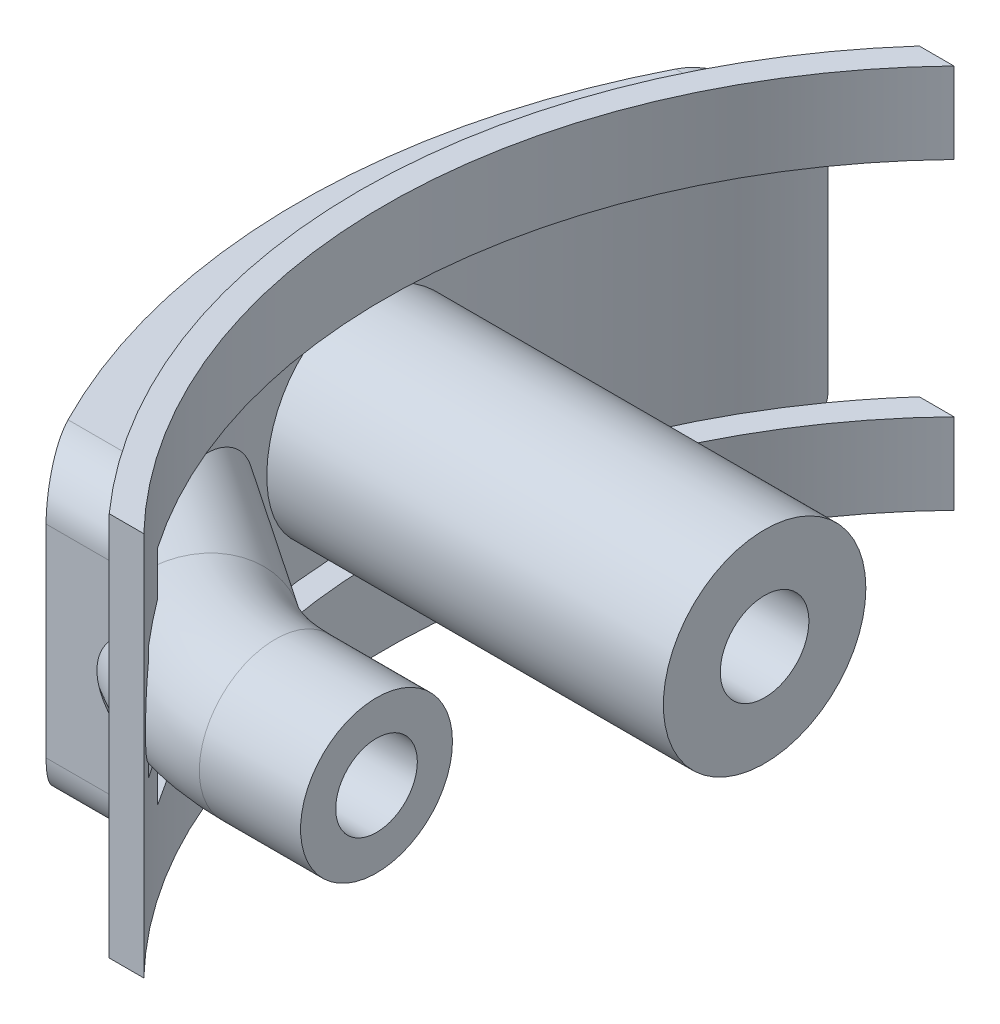
SolidWorks part; units mm, degrees
ref_plane "Front Plane" through (0, 0, 0) normal (0, 0, 1) x (1, 0, 0)
ref_plane "Top Plane" through (0, 0, 0) normal (0, 1, 0) x (1, 0, 0)
ref_plane "Right Plane" through (0, 0, 0) normal (1, 0, 0) x (0, 0, -1)
sketch "Sketch1" plane through (0, 0, 0) normal (0, 1, 0) x (1, 0, 0)
  line L0 (-71.0633, 44.45) -> (-61.8921, 44.45)
  line L1 (-71.0633, -44.45) -> (-61.8921, -44.45)
  line L2 (0, 0) -> (-76.2, 0) construction
  arc A0 (-71.0633, 44.45) -> (-71.0633, -44.45) centre (0, 0) ccw
  arc A1 (-61.8921, 44.45) -> (-61.8921, -44.45) centre (0, 0) ccw
  dimension "D1" = 167.64
  dimension "D2" = 152.4
  dimension "D3" = 88.9
extrude "Boss-Extrude1" add sketch "Sketch1" along normal blind 19.05 and the other way blind 19.05
sketch "Sketch14" plane through (0, 0, 0) normal (1, 0, 0) x (0, 0, -1)
  line L0 (-44.45, -19.05) -> (-44.45, 19.05) construction
  line L1 (-50.8, 24.13) -> (50.8, 24.13)
  line L2 (-50.8, 24.13) -> (-50.8, 13.97)
  line L3 (-50.8, 13.97) -> (50.8, 13.97)
  line L4 (50.8, 24.13) -> (50.8, 13.97)
  line L5 (44.45, -19.05) -> (44.45, 19.05) construction
  line L6 (-50.8, 19.05) -> (50.8, 19.05) construction
  line L7 (44.45, 19.05) -> (-44.45, 19.05) construction
  line L8 (-49.7824, 0) -> (49.7824, 0) construction
  line L9 (-50.8, -19.05) -> (50.8, -19.05) construction
  line L10 (50.8, -24.13) -> (50.8, -13.97)
  line L11 (-50.8, -13.97) -> (50.8, -13.97)
  line L12 (-50.8, -24.13) -> (-50.8, -13.97)
  line L13 (-50.8, -24.13) -> (50.8, -24.13)
  dimension "D1" = 10.16
  dimension "D2" = 6.35
  dimension "D3" = 6.35
extrude "Boss-Extrude11" add sketch "Sketch14" against normal up to surface (5.9961 mm away) from offset 50.8 up to face at (-69.0461, 0, 0) offset against normal yes
sketch "Sketch15" plane through (0, 24.13, 0) normal (0, 1, 0) x (1, 0, 0)
  line L0 (-51.6365, -51.6365) -> (-53.8815, -53.8815)
  line L1 (-53.8815, 53.8815) -> (-51.6365, 51.6365)
  line L2 (0, 0) -> (-123.1347, 0) construction
  arc A0 (-51.6365, 51.6365) -> (-51.6365, -51.6365) centre (0, 0) ccw
  arc A1 (-56.7961, 50.8) -> (-56.7961, -50.8) centre (0, 0) ccw construction
  arc A2 (-53.8815, -53.8815) -> (-53.8815, 53.8815) centre (0, 0) ccw
  dimension "D1" = 146.05
  dimension "D2" = 90
extrude "Cut-Extrude1" cut sketch "Sketch15" against normal up to next
sketch "Sketch17" plane through (0, 13.97, 0) normal (0, -1, 0) x (1, 0, 0)
  line L0 (-64.0532, 41.275) -> (-60.2414, 41.275)
  line L1 (-56.7961, 50.8) -> (-52.4596, 50.8) construction
  line L3 (-52.4596, 50.8) -> (-56.7961, 50.8)
  arc A0 (-61.8921, 44.45) -> (-61.8921, -44.45) centre (0, 0) ccw construction
  arc A1 (-52.4596, 50.8) -> (-52.4596, -50.8) centre (0, 0) ccw construction
  arc A2 (-52.4596, 50.8) -> (-60.2414, 41.275) centre (0, 0) ccw
  arc A4 (-64.0532, 41.275) -> (-56.7961, 50.8) centre (0, 0) cw
  dimension "D1" = 9.525
extrude "Boss-Extrude12" add sketch "Sketch17" along normal up to surface (27.94 mm away) up to face at (-58.909, -13.97, 0)
mirror "Mirror4" about plane through (0, 0, 0) normal (0, 1, 0) of "Cut-Extrude1"
sketch "Sketch2" plane through (0, 0, 0) normal (1, 0, 0) x (0, 0, -1)
  circle A0 centre (0, 0) radius 12.7
  dimension "D1" = 25.4
extrude "Boss-Extrude2" add sketch "Sketch2" against normal up to surface (49.7342 mm away) from offset 25.4 up to face at (-69.5742, 0, -1.7539) offset against normal yes
ref_axis "Axis1" through (0, -13.97, 0) along (0, 1, 0)
sketch "Sketch6" plane through (0, 0, 0) normal (0, 1, 0) x (1, 0, 0)
  line L0 (0, 0) -> (-83.82, 0) construction
  line L1 (-25.4, 5.5562) -> (-51.2095, 5.5562)
  line L2 (-25.4, -12.7) -> (-25.4, 12.7) construction
  line L3 (-57.5595, 3.8548) -> (-60.2451, 2.3042)
  line L4 (-61.2611, 0) -> (-61.2611, 2.032) construction
  line L5 (-62.05, 2.1359) -> (-83.4497, 7.8699)
  line L6 (-25.4, 5.5562) -> (-25.4, 0)
  line L7 (-25.4, 0) -> (-83.82, 0)
  line L8 (-83.82, 0) -> (-83.82, 7.8699)
  line L9 (-83.82, 7.8699) -> (-83.4497, 7.8699)
  arc A0 (-71.0633, 44.45) -> (-71.0633, -44.45) centre (0, 0) ccw construction
  arc A1 (-61.2611, 2.032) -> (-60.2451, 2.3042) centre (-61.2611, 4.064) ccw
  arc A2 (-62.05, 2.1359) -> (-61.2611, 2.032) centre (-61.2611, 5.08) ccw
  arc A3 (-51.2095, 5.5562) -> (-57.5595, 3.8548) centre (-51.2095, -7.1438) ccw
  dimension "D2" = 2.032
  dimension "D3" = 3.048
  dimension "D7" = 12.7
  dimension "D1" = 2.032
  dimension "D4" = 15
  dimension "D5" = 7.8699
  dimension "D6" = 5.5562
  dimension "D8" = 30
revolve "Cut-Revolve1" cut sketch "Sketch6" angle 360 about L0
ref_plane "Plane3" through (0, 0, 0) normal (-0.829, 0, -0.5592) x (-0.5592, 0, 0.829)
sketch "Sketch7" plane through (0, 0, 0) normal (-0.829, 0, -0.5592) x (-0.5592, 0, 0.829)
  line L0 (0, -13.97) -> (0, 13.97) construction
  circle A0 centre (63.5, 0) radius 9.525
  dimension "D1" = 19.05
  dimension "D2" = 63.5
extrude "Boss-Extrude4" add sketch "Sketch7" along normal up to surface (0.1767 mm away) from offset 21.59 up to face at (-75.1836, -2.7246, 12.4043)
sketch "Sketch10" plane through (0, 0, 0) normal (0, 1, 0) x (1, 0, 0)
  line L0 (-59.7733, -36.2772) -> (-80.8681, -22.0486) construction
  line L1 (-48.0814, -32.6743) -> (-74.7746, -14.6695) construction
  line L2 (-58.7025, -30.8251) -> (-61.0346, -29.2521) construction
  line L4 (-58.7025, -30.8251) -> (-56.2386, -27.1722)
  line L5 (-65.8043, -28.6539) -> (-66.8203, -28.6539)
  line L6 (-67.9566, -28.3065) -> (-69.0928, -29.9911) construction
  line L7 (-66.2521, -25.7796) -> (-67.9566, -28.3065) construction
  line L8 (-83.0873, -11.059) -> (-68.5525, -27.7793)
  line L9 (-83.0873, -11.059) -> (-87.488, -17.5834)
  line L10 (-87.488, -17.5834) -> (-59.7733, -36.2772)
  line L11 (-48.0814, -32.6743) -> (-53.4077, -40.5709)
  line L12 (-53.4077, -40.5709) -> (-59.7733, -36.2772)
  line L15 (-56.2386, -27.1722) -> (-48.0814, -32.6743)
  line L16 (-48.0814, -32.6743) -> (-74.7746, -14.6695) construction
  line L17 (-56.9085, -45.7611) -> (-48.0814, -32.6743) construction
  line L23 (-52.1835, -41.3966) -> (-80.8681, -22.0486) construction
  line L32 (-48.0814, -32.6743) -> (-74.7746, -14.6695) construction
  arc A0 (-71.0633, 44.45) -> (-71.0633, -44.45) centre (0, 0) ccw construction
  arc A1 (-67.9566, -28.3065) -> (-66.8203, -28.6539) centre (-66.8203, -26.6219) ccw
  arc A2 (-68.5525, -27.7793) -> (-67.9566, -28.3065) centre (-66.2521, -25.7796) ccw
  arc A3 (-58.7025, -30.8251) -> (-65.8043, -28.6539) centre (-65.8043, -41.3539) ccw
  dimension "D2" = 2.032
  dimension "D3" = 3.048
  dimension "D7" = 12.7
  dimension "D1" = 2.032
  dimension "D4" = 15
  dimension "D5" = 7.8699
  dimension "D6" = 5.5562
  dimension "D8" = 1.016
  dimension "D9" = 63.5
revolve "Cut-Revolve2" cut sketch "Sketch10" angle 360 about L10
sketch "Sketch8" plane through (0, 0, 0) normal (0, 1, 0) x (1, 0, 0)
  line L1 (-56.2386, -27.1722) -> (-66.6314, -42.5802) construction
  line L2 (-47.3614, -39.4112) -> (-34.6614, -39.4112)
  line L4 (-61.5649, -35.0688) -> (-51.2708, -42.0122) construction
  line L16 (-64.8733, -39.9737) -> (-56.2386, -27.1722) construction
  line L18 (-64.4273, -39.3124) -> (-58.7025, -30.8251) construction
  arc A0 (-61.5649, -35.0688) -> (-47.3614, -39.4112) centre (-47.3614, -14.0112) ccw
  dimension "D1" = 25.4
  dimension "D2" = 12.7
sketch "Sketch18" plane through (-26.0562, 0, -17.5751) normal (0.829, 0, 0.5592) x (0.5592, 0, -0.829)
  circle A0 centre (-63.5, 0) radius 9.525
  circle A1 centre (-63.5, 0) radius 5.1188
  circle A2 centre (-63.5, 0) radius 5.1188 construction
  arc A3 (-69.4164, -7.4647) -> (-69.4164, 7.4647) centre (-63.5, 0) ccw construction
fillet "Fillet2" radius 6.35 4 edges at (-66.4777, -19.05, 44.45) (-66.4777, 19.05, 44.45) (-66.4777, 19.05, -44.45) (-66.4777, -19.05, -44.45)
sweep "Sweep1" add profiles "Sketch18" path "Sketch8"
equation "\"D2@Sketch6\"=\"D1@Sketch6\""
equation "\"D3@Sketch6\"=1.5*\"D1@Sketch6\""
equation "\"D5@Sketch6\"  = \"D1@Sketch6\" * ( \"ER_pitch\" ) ^ .5"
equation "\"D2@Sketch10\"=\"D1@Sketch10\""
equation "\"D3@Sketch10\"=1.5*\"D1@Sketch10\""
equation "\"D5@Sketch10\" = \"D1@Sketch10\" * ( \"ER_roll\" ) ^ .5"
equation "\"ER_roll\"  = 15"
equation "\"ER_pitch\" = 15"
